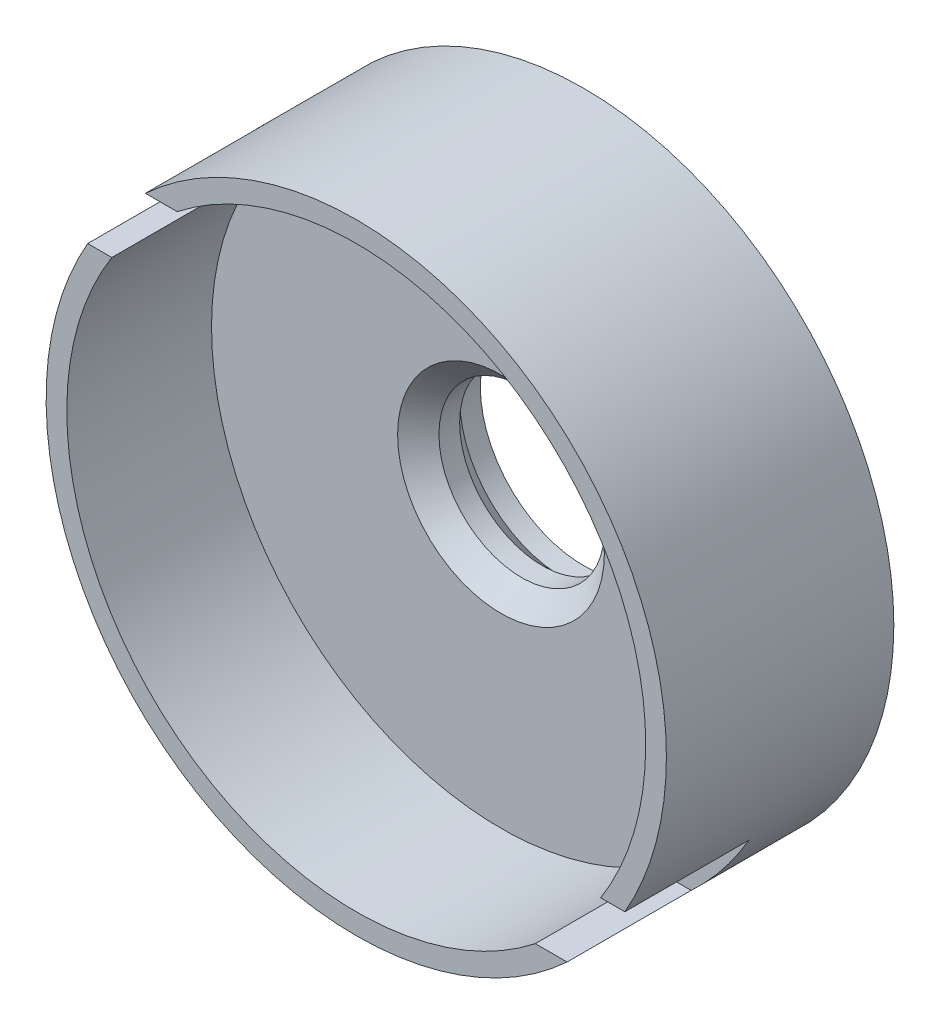
SolidWorks part; units mm, degrees
ref_plane "Спереди" through (0, 0, 0) normal (0, 0, 1) x (1, 0, 0)
ref_plane "Сверху" through (0, 0, 0) normal (0, 1, 0) x (1, 0, 0)
ref_plane "Справа" through (0, 0, 0) normal (1, 0, 0) x (0, 0, -1)
sketch "Эскиз5" plane through (0, 0, 0) normal (0, 0, 1) x (1, 0, 0)
  circle A0 centre (0, 0) radius 30
  dimension "D1" = 60
extrude "Бобышка-Вытянуть1" add sketch "Эскиз5" along normal blind 20 and the other way blind 2
sketch "Эскиз6" plane through (0, 0, 0) normal (0, 0, 1) x (1, 0, 0)
  circle A0 centre (0, 0) radius 28
  dimension "D1" = 56
extrude "Вырез-Вытянуть1" cut sketch "Эскиз6" along normal blind 14 from offset 6
sketch "Эскиз7" plane through (0, 0, 0) normal (0, 0, 1) x (1, 0, 0)
  circle A0 centre (0, 0) radius 8
  dimension "D1" = 16
extrude "Вырез-Вытянуть2" cut sketch "Эскиз7" along normal blind 15 and the other way blind 2
sketch "Эскиз8" plane through (0, 0, 0) normal (0, 0, 1) x (1, 0, 0)
  circle A0 centre (0, 0) radius 10.25
  dimension "D1" = 20.5
sketch "Эскиз10" plane through (0, 0, 0) normal (0, 0, 1) x (1, 0, 0)
  line L1 (-30, 15) -> (-15, 15)
  line L2 (-30, 15) -> (-30, 22)
  line L3 (-30, 22) -> (-15, 22)
  line L4 (-15, 15) -> (-15, 22)
  dimension "D1" = 15
  dimension "D2" = 15
  dimension "D3" = 7
  dimension "D4" = 15
extrude "Вырез-Вытянуть4" cut sketch "Эскиз10" along normal blind 12 from offset 8
sketch "Эскиз13" plane through (0, 0, 0) normal (0, 0, 1) x (1, 0, 0)
  line L1 (15, -15) -> (30, -15)
  line L2 (15, -15) -> (15, -22)
  line L3 (15, -22) -> (30, -22)
  line L4 (30, -15) -> (30, -22)
  dimension "D1" = 15
  dimension "D2" = 15
  dimension "D3" = 15
  dimension "D4" = 7
extrude "Вырез-Вытянуть5" cut sketch "Эскиз13" along normal blind 12 from offset 8
sketch "Эскиз14" plane through (0, 0, 0) normal (0, 0, 1) x (1, 0, 0)
  circle A0 centre (0, 0) radius 10.5
  dimension "D1" = 21
sketch "Эскиз15" plane through (0, 0, 0) normal (1, 0, 0) x (0, 0, -1)
  line L6 (0, 10.25) -> (0, -10.25) construction
  line L9 (0, 0) -> (-12.4767, 0) construction
  line L15 (-6, 8) -> (-4, 8)
  line L16 (2, 8) -> (-6, 8) construction
  line L17 (-4, 8) -> (-6, 10)
  line L18 (-6, 28) -> (-6, -28) construction
  line L19 (-6, 10) -> (-6, 8)
  line L20 (2, 8) -> (2, 10)
  line L21 (2, -30) -> (2, 30) construction
  line L22 (2, 10) -> (0, 10)
  line L23 (0, 10) -> (-2, 8)
  line L24 (-2, 8) -> (2, 8)
  dimension "D1" = 2
  dimension "D2" = 2
  dimension "D3" = 2
  dimension "D4" = 2
revolve "Вырез-Повернуть1" cut sketch "Эскиз15" angle 360 about L9
